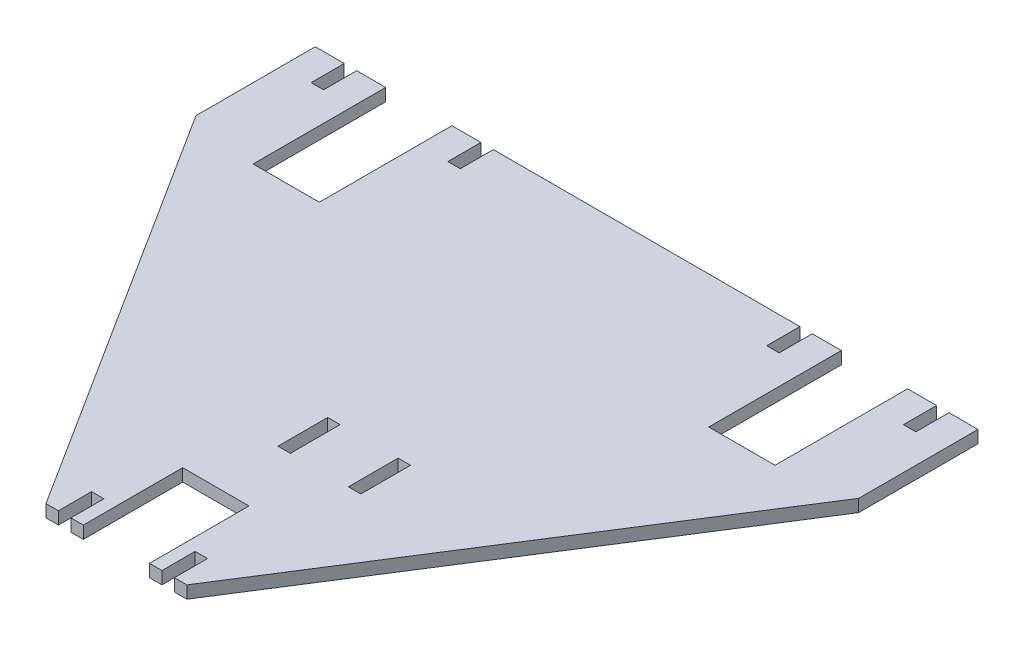
SolidWorks part; units mm, degrees
ref_plane "Front Plane" through (0, 0, 0) normal (0, 0, 1) x (1, 0, 0)
ref_plane "Top Plane" through (0, 0, 0) normal (0, 1, 0) x (1, 0, 0)
ref_plane "Right Plane" through (0, 0, 0) normal (1, 0, 0) x (0, 0, -1)
sketch "Sketch1" plane through (0, 0, 0) normal (0, 1, 0) x (1, 0, 0)
  line L0 (0, 0) -> (0, -142.875) construction
  line L1 (12.7, -63.5) -> (-12.7, -63.5)
  line L2 (-12.7, -63.5) -> (-12.7, -101.6)
  line L3 (-12.7, -101.6) -> (-17.4625, -101.6)
  line L4 (-26.9875, -101.6) -> (-127, 55.88)
  line L5 (-127, 55.88) -> (-127, 101.6)
  line L6 (-127, 101.6) -> (-115.8875, 101.6)
  line L7 (-100.0125, 101.6) -> (-100.0125, 50.8)
  line L9 (-100.0125, 50.8) -> (-74.6125, 50.8)
  line L10 (-74.6125, 50.8) -> (-74.6125, 101.6)
  line L11 (-74.6125, 101.6) -> (-63.5, 101.6)
  line L13 (74.6125, 50.8) -> (74.6125, 101.6)
  line L14 (100.0125, 50.8) -> (74.6125, 50.8)
  line L15 (100.0125, 101.6) -> (100.0125, 50.8)
  line L16 (127, 101.6) -> (115.8875, 101.6)
  line L17 (127, 55.88) -> (127, 101.6)
  line L18 (26.9875, -101.6) -> (127, 55.88)
  line L19 (12.7, -101.6) -> (17.4625, -101.6)
  line L20 (12.7, -63.5) -> (12.7, -101.6)
  line L21 (-127, 101.6) -> (127, -101.6) construction
  line L22 (-22.225, -101.6) -> (-26.9875, -101.6)
  line L24 (-22.225, -101.6) -> (-22.225, -88.9)
  line L25 (-22.225, -88.9) -> (-17.4625, -88.9)
  line L26 (-17.4625, -101.6) -> (-17.4625, -88.9)
  line L27 (22.225, -101.6) -> (22.225, -88.9)
  line L28 (22.225, -88.9) -> (17.4625, -88.9)
  line L29 (17.4625, -101.6) -> (17.4625, -88.9)
  line L30 (22.225, -101.6) -> (26.9875, -101.6)
  line L31 (-87.3125, 50.8) -> (-87.3125, 101.6) construction
  line L32 (-111.125, 101.6) -> (-100.0125, 101.6)
  line L34 (-115.8875, 101.6) -> (-115.8875, 88.9)
  line L35 (-115.8875, 88.9) -> (-111.125, 88.9)
  line L36 (-111.125, 101.6) -> (-111.125, 88.9)
  line L37 (-58.7375, 101.6) -> (-58.7375, 88.9)
  line L38 (-58.7375, 88.9) -> (-63.5, 88.9)
  line L39 (-63.5, 101.6) -> (-63.5, 88.9)
  line L40 (-58.7375, 101.6) -> (58.7375, 101.6)
  line L41 (115.8875, 101.6) -> (115.8875, 88.9)
  line L42 (115.8875, 88.9) -> (111.125, 88.9)
  line L43 (111.125, 101.6) -> (111.125, 88.9)
  line L44 (58.7375, 101.6) -> (58.7375, 88.9)
  line L45 (63.5, 101.6) -> (63.5, 88.9)
  line L46 (58.7375, 88.9) -> (63.5, 88.9)
  line L47 (63.5, 101.6) -> (74.6125, 101.6)
  line L48 (111.125, 101.6) -> (100.0125, 101.6)
  point P26 (0, -63.5)
  dimension "D2" = 25.4
  dimension "D3" = 254
  dimension "D5" = 38.1
  dimension "D6" = 50.8
  dimension "D7" = 203.2
  dimension "D8" = 45.72
  dimension "D9" = 26.9875
  dimension "D4" = 14.2875
  dimension "D10" = 4.7625
  dimension "D11" = 12.7
  dimension "D12" = 4.7625
extrude "Boss-Extrude1" add sketch "Sketch1" along normal blind 4.7625 contours L13 L47 L45 L46 L44 L40 L37 L38 L39 L11 L10 L9 L7 L32 L36 L35 L34 L6 L5 L4 L22 L24 L25 L26 L3 L2 L1 L20 L19 L29 L28 L27 L30 L18 L17 L16 L41 L42 L43 L48 L15 L14
sketch "Sketch2" plane through (0, 4.7625, 0) normal (0, 1, 0) x (1, 0, 0)
  line L0 (14.2875, 0) -> (14.2875, 54.8341) construction
  line L6 (-58.7375, 88.9) -> (-63.5, 88.9) construction
  line L7 (-1.5875, -19.05) -> (3.175, -19.05)
  line L8 (-1.5875, -19.05) -> (-1.5875, -38.1)
  line L9 (-1.5875, -38.1) -> (3.175, -38.1)
  line L10 (3.175, -19.05) -> (3.175, -38.1)
  line L12 (25.4, -19.05) -> (25.4, -38.1)
  line L13 (30.1625, -38.1) -> (25.4, -38.1)
  line L14 (30.1625, -19.05) -> (30.1625, -38.1)
  line L15 (30.1625, -19.05) -> (25.4, -19.05)
  line L17 (12.7, -63.5) -> (-12.7, -63.5) construction
  dimension "D2" = 25.4
  dimension "D4" = 14.2875
  dimension "D3" = 31.75
  dimension "D1" = 19.05
extrude "Cut-Extrude1" cut sketch "Sketch2" against normal through all
equation "\"D1@Boss-Extrude1\"=\"thick@FullAssem.Assembly\""
equation "\"D4@Sketch1\"=\"thick@FullAssem.Assembly\"*3"
equation "\"D10@Sketch1\"=\"thick@FullAssem.Assembly\""
equation "\"D9@Sketch1\"=\"thick@FullAssem.Assembly\"*3+0.5"
equation "\"D12@Sketch1\"=\"thick@FullAssem.Assembly\""
equation "\"D3@Sketch2\"=\"MotorLength@Motor-1.Part\""
equation "\"D1@Sketch2\" =  ( \"MotorDiameter@Motor<1>.Part\" + 0.5 )  / 2"
equation "\"D4@Sketch2\"=-3*\"thick@FullAssem.Assembly\""
